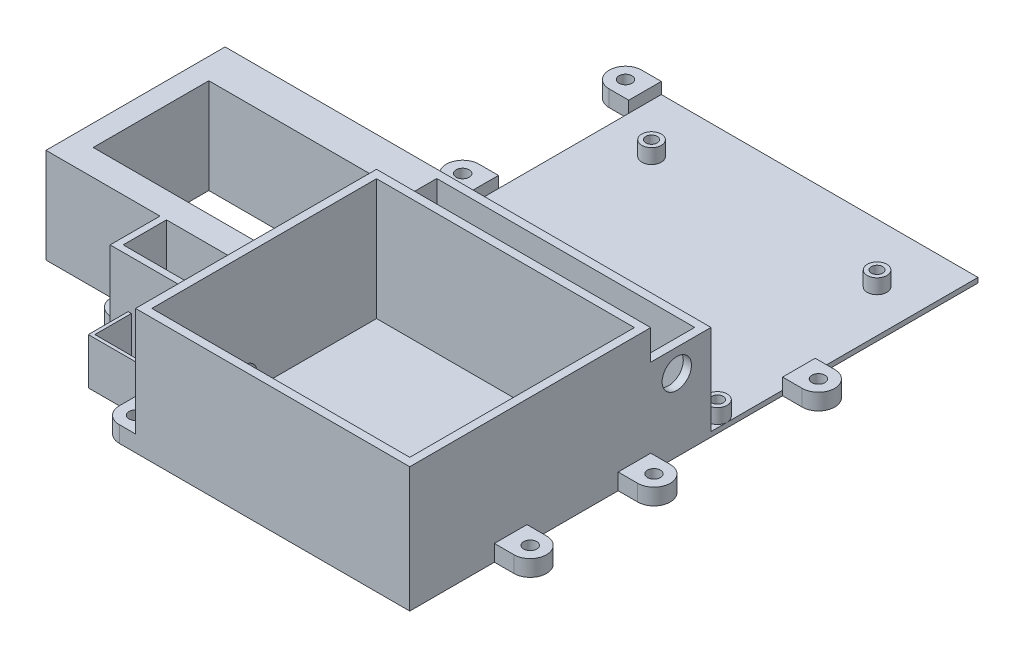
SolidWorks part; units mm, degrees
ref_plane "Front Plane" through (0, 0, 0) normal (0, 0, 1) x (1, 0, 0)
ref_plane "Top Plane" through (0, 0, 0) normal (0, 1, 0) x (1, 0, 0)
ref_plane "Right Plane" through (0, 0, 0) normal (1, 0, 0) x (0, 0, -1)
sketch "Sketch1" plane through (0, 0, 0) normal (0, 1, 0) x (1, 0, 0)
  line L0 (-39.6, 37) -> (86.5346, 37) construction
  line L1 (-39.6, -34.5) -> (39.6, -34.5)
  line L2 (-39.6, -34.5) -> (-39.6, 34.5)
  line L3 (-39.6, 34.5) -> (39.6, 34.5)
  line L4 (39.6, -34.5) -> (39.6, 34.5)
  line L5 (-39.6, -34.5) -> (39.6, 34.5) construction
  line L6 (-39.6, 34.5) -> (39.6, -34.5) construction
  line L7 (-42.1, -37) -> (42.1, -37)
  line L8 (-42.1, -37) -> (-42.1, 37)
  line L9 (-42.1, 37) -> (42.1, 37)
  line L10 (42.1, -37) -> (42.1, 37)
  line L11 (-42.1, -37) -> (42.1, 37) construction
  line L12 (-42.1, 37) -> (42.1, -37) construction
  line L13 (-42.1, -37) -> (77.4846, -37) construction
  line L14 (-55.15, 55.5) -> (-107.1, 55.5)
  line L15 (-107.1, 55.5) -> (-107.1, 0.5)
  line L16 (39.6, 0) -> (-39.6, 0) construction
  line L17 (48.1, 37) -> (42.1, 37)
  line L18 (42.1, 37) -> (48.1, 37)
  line L19 (48.1, 27) -> (42.1, 27)
  line L20 (-42.1, -37) -> (-47.1, -37)
  line L21 (-47.1, -27) -> (-42.1, -27)
  line L22 (48.1, -37) -> (42.1, -37) construction
  line L23 (48.1, -27) -> (42.1, -27) construction
  line L24 (39.6, 37) -> (39.6, 53)
  line L25 (39.6, 53) -> (-39.6, 53)
  line L26 (-39.6, 53) -> (-39.6, 37)
  line L27 (77.4846, -19) -> (-39.6, -19) construction
  line L28 (48.1, -1) -> (42.1, -1)
  line L29 (48.1, -11) -> (42.1, -11)
  line L30 (42.1, 37) -> (42.1, 55.5)
  line L31 (42.1, 55.5) -> (-42.1, 55.5)
  line L32 (-107.1, 55.5) -> (-55.15, 55.5)
  line L33 (42.1, 119.5) -> (-55.15, 119.5) construction
  line L34 (42.1, 55.5) -> (-55.15, 55.5)
  line L35 (42.1, 55.5) -> (42.1, 137.5)
  line L36 (42.1, 137.5) -> (-55.15, 137.5)
  line L37 (-55.15, 55.5) -> (-55.15, 137.5)
  line L38 (42.1, 60.5) -> (-55.15, 60.5) construction
  line L39 (42.1, 77.5) -> (48.1, 77.5)
  line L40 (42.1, 87.5) -> (48.1, 87.5)
  line L41 (-6.525, 137.5) -> (-6.525, 55.5) construction
  line L42 (48.1, 32) -> (48.1, 95.8238) construction
  line L43 (-55.15, 77.5) -> (-61.15, 77.5)
  line L44 (-55.15, 87.5) -> (-61.15, 87.5)
  line L45 (-61.15, 82.5) -> (-61.15, 137.5) construction
  line L46 (-61.15, 137.5) -> (-55.15, 137.5)
  line L47 (-61.15, 127.5) -> (-55.15, 127.5)
  line L48 (-107.1, 55.5) -> (-107.1, 60.5)
  line L49 (-97.1, 60.5) -> (-97.1, 55.5)
  line L50 (-100.6, 44) -> (-48.6, 44)
  line L51 (-48.6, 44) -> (-48.6, 8.5)
  line L52 (-48.6, 8.5) -> (-100.6, 8.5)
  line L53 (-100.6, 8.5) -> (-100.6, 44)
  line L54 (-42.1, -12.8) -> (-70.1, -12.8)
  line L55 (-70.1, -12.8) -> (-70.1, 0.5)
  line L56 (-107.1, 0.5) -> (-42.1, 0.5)
  line L57 (-72.1, 0.5) -> (-72.1, -14.8)
  line L58 (-72.1, -14.8) -> (-42.1, -14.8)
  line L59 (-42.1, -26) -> (-65.6, -26)
  line L60 (-65.6, -26) -> (-65.6, -14.8)
  line L61 (-47.1, -27) -> (-66.6, -27)
  line L62 (-66.6, -27) -> (-66.6, -14.8)
  line L63 (-82.1, -4.5) -> (-82.1, 0.5)
  line L64 (-52.1, -32) -> (-52.1, -27)
  line L65 (-77.1, -9.5) -> (-72.1, -9.5)
  circle A2 centre (-102.1, 60.5) radius 2
  circle A3 centre (48.1, 32) radius 2
  arc A4 (48.1, 37) -> (48.1, 27) centre (48.1, 32) cw
  circle A5 centre (-47.1, -32) radius 2
  arc A6 (-47.1, -37) -> (-52.1, -32) centre (-47.1, -32) cw
  circle A7 centre (48.1, -32) radius 2 construction
  arc A8 (48.1, -37) -> (48.1, -27) centre (48.1, -32) ccw construction
  circle A9 centre (48.1, -6) radius 2
  arc A10 (48.1, -1) -> (48.1, -11) centre (48.1, -6) cw
  circle A11 centre (29.1, 119.5) radius 1.75
  circle A12 centre (39.1, 60.5) radius 1.75
  circle A13 centre (-52.15, 60.5) radius 1.75
  circle A14 centre (-40.15, 119.5) radius 1.75
  circle A15 centre (39.1, 60.5) radius 3
  circle A16 centre (-52.15, 60.5) radius 3
  circle A17 centre (-40.15, 119.5) radius 3
  circle A18 centre (29.1, 119.5) radius 3
  circle A19 centre (48.1, 82.5) radius 2
  arc A20 (48.1, 87.5) -> (48.1, 77.5) centre (48.1, 82.5) cw
  circle A21 centre (-61.15, 82.5) radius 2
  arc A22 (-61.15, 87.5) -> (-61.15, 77.5) centre (-61.15, 82.5) ccw
  circle A23 centre (-61.15, 132.5) radius 2
  arc A24 (-61.15, 137.5) -> (-61.15, 127.5) centre (-61.15, 132.5) ccw
  arc A26 (-107.1, 60.5) -> (-97.1, 60.5) centre (-102.1, 60.5) cw
  circle A27 centre (-77.1, -4.5) radius 2
  arc A28 (-77.1, -9.5) -> (-82.1, -4.5) centre (-77.1, -4.5) cw
  point P0 (0, 0)
  point P6 (0, 0)
  point P24 (0, 0)
  point P111 (-76.7705, -9.4891)
  dimension "D5" = 4
  dimension "D6" = 5
  dimension "D7" = 4
  dimension "D8" = 5
  dimension "D19" = 3.5
  dimension "D20" = 3.5
  dimension "D23" = 3.5
  dimension "D24" = 3.5
  dimension "D28" = 6
  dimension "D29" = 6
  dimension "D10" = 4
  dimension "D30" = 5
  dimension "D32" = 4
  dimension "D33" = 5
  dimension "D36" = 52
  dimension "D37" = 65
  dimension "D38" = 35.5
  dimension "D39" = 55
  dimension "D34" = 5
  dimension "D43" = 4
  dimension "D44" = 5
  dimension "D53" = 5
  dimension "D54" = 4
  dimension "D1" = 2.5
  dimension "D2" = 2.5
  dimension "D3" = 69
  dimension "D4" = 79.2
  dimension "D9" = 6
  dimension "D11" = 16
  dimension "D12" = 19
  dimension "D13" = 2.5
  dimension "D14" = 2.5
  dimension "D15" = 55
  dimension "D16" = 82
  dimension "D17" = 97.25
  dimension "D18" = 18
  dimension "D21" = 13
  dimension "D22" = 15
  dimension "D25" = 3
  dimension "D26" = 3
  dimension "D27" = 5
  dimension "D31" = 60
  dimension "D35" = 0
  dimension "D40" = 8
  dimension "D41" = 6.5
  dimension "D42" = 0
  dimension "D45" = 5
  dimension "D46" = 2
  dimension "D47" = 2
  dimension "D48" = 28
  dimension "D49" = 13.3
  dimension "D50" = 11.2
  dimension "D51" = 23.5
  dimension "D52" = 1
  dimension "D55" = 5
extrude "Boss-Extrude1" add sketch "Sketch1" along normal blind 1.2 contours L1 L4 L3 L2 | L56 L55 L54 L8 | L60 L59 L8 L58 region at (0, 0, 0) region at (-53.85, 0, 20.4) region at (-56.1, 0, 6.15)
extrude "Boss-Extrude2" add sketch "Sketch1<3>" along normal blind 38.4 contours L7 L10 L9 L8 L4 L1 L2 L3 region at (-40.979, 0, 32)
sketch "Sketch1<3>" plane through (0, 0, 0) normal (0, 1, 0) x (1, 0, 0) same geometry as "Sketch1"
extrude "Boss-Extrude3" add sketch "Sketch1<4>" along normal blind 5 contours A6 L20 L8 L21 A5 | L22 A8 L23 L10 A7 | A4 L17 L10 L19 A3 | A20 L40 L35 L39 A19 | L44 A22 L43 L37 A21 | L46 A24 L47 L37 A23 | A26 L48 L32 L49 A2 | A28 L57 L56 L63 A27 region at (-44.6, 0, 36.8586) region at (42.2487, 0, 6) region at (42.2487, 0, -32) region at (-72.2414, 0, 4.5) region at (42.2487, 0, -82.5) region at (-102.1, 0, -55.6414) region at (-58.15, 0, -77.6487) region at (-55.2987, 0, -132.5)
sketch "Sketch1<4>" plane through (0, 0, 0) normal (0, 1, 0) x (1, 0, 0) same geometry as "Sketch1"
sketch "Sketch2" plane through (-42.1, 0, 0) normal (-1, 0, 0) x (0, 0, 1)
  line L0 (37, 38.4) -> (37, 5) construction
  line L1 (6.15, 1.2) -> (6.15, 12.2165) construction
  line L2 (12.8, 1.2) -> (-0.5, 1.2) construction
  line L3 (20.4, 1.2) -> (20.4, 12.2165) construction
  line L4 (26, 1.2) -> (14.8, 1.2) construction
  line L6 (27, 0) -> (-37, 0) construction
  circle A0 centre (31, 19.65) radius 3
  circle A1 centre (6.15, 5.2) radius 4
  circle A2 centre (20.4, 4.2) radius 3
  dimension "D2" = 6
  dimension "D4" = 4
  dimension "D6" = 8
  dimension "D7" = 6
  dimension "D1" = 19.65
  dimension "D3" = 6
  dimension "D5" = 3
extrude "Cut-Extrude1" cut sketch "Sketch2" against normal blind 5
extrude "Boss-Extrude4" add sketch "Sketch1<5>" along normal blind 29.2 contours L31 L9 L26 L25 L24 L30 region at (40.85, 0, -38.5901)
sketch "Sketch1<5>" plane through (0, 0, 0) normal (0, 1, 0) x (1, 0, 0) same geometry as "Sketch1"
extrude "Boss-Extrude5" add sketch "Sketch1<6>" along normal blind 1.2 contours L25 L26 L9 L24 region at (0, 0, -45)
sketch "Sketch1<6>" plane through (0, 0, 0) normal (0, 1, 0) x (1, 0, 0) same geometry as "Sketch1"
sketch "Sketch3" plane through (39.6, 0, 0) normal (-1, 0, 0) x (0, 0, 1)
  line L0 (-37, 15.2) -> (-53, 15.2) construction
  line L1 (-37, 29.2) -> (-37, 1.2) construction
  line L2 (-53, 29.2) -> (-53, 1.2) construction
  line L3 (-53, 15.2) -> (-37, 1.2) construction
  line L4 (-55.5, 29.2) -> (-0.5, 29.2) construction
  line L5 (-55.5, 29.2) -> (-55.5, 0) construction
  circle A1 centre (-45, 22.2) radius 4.5
  dimension "D1" = 9
  dimension "D2" = 7
  dimension "D3" = 10.5
extrude "Boss-Extrude9" add sketch "Sketch1<9>" along normal blind 1.5 contours L37 A16 L34 L31 L35 A15 L36 A18 A17 | A15 A12 | A18 A11 | A17 A14 | A16 A13 region at (36.1849, 0, -60.5) region at (-52.15, 0, -63.4151) region at (-6.5322, 0, -96.5935) region at (-43.0651, 0, -119.5) region at (26.1849, 0, -119.5)
sketch "Sketch1<9>" plane through (0, 0, 0) normal (0, 1, 0) x (1, 0, 0) same geometry as "Sketch1"
extrude "Boss-Extrude10" add sketch "Sketch1<10>" along normal blind 6 contours A17 A14 | A16 A13 | A15 A12 | A18 A11 region at (36.1849, 0, -60.5) region at (-52.15, 0, -63.4151) region at (-43.0651, 0, -119.5) region at (26.1849, 0, -119.5)
sketch "Sketch1<10>" plane through (0, 0, 0) normal (0, 1, 0) x (1, 0, 0) same geometry as "Sketch1"
extrude "Boss-Extrude11" add sketch "Sketch1<11>" along normal blind 19 contours L15 L56 L8 L14 L52 L53 L50 L51 region at (40.85, 0, -38.5901)
sketch "Sketch1<11>" plane through (0, 0, 0) normal (0, 1, 0) x (1, 0, 0) same geometry as "Sketch1"
extrude "Cut-Extrude2" cut sketch "Sketch3" against normal blind 10
extrude "Boss-Extrude12" add sketch "Sketch1<12>" along normal blind 29.2 contours L57 L58 L8 L54 L55 L56 region at (-53.85, 0, 14.4632)
sketch "Sketch1<12>" plane through (0, 0, 0) normal (0, 1, 0) x (1, 0, 0) same geometry as "Sketch1"
extrude "Boss-Extrude13" add sketch "Sketch1<13>" along normal blind 14.2 contours L62 L61 L21 L8 L59 L60 L58 region at (-44.6, 0, 26.7263)
sketch "Sketch1<13>" plane through (0, 0, 0) normal (0, 1, 0) x (1, 0, 0) same geometry as "Sketch1"
